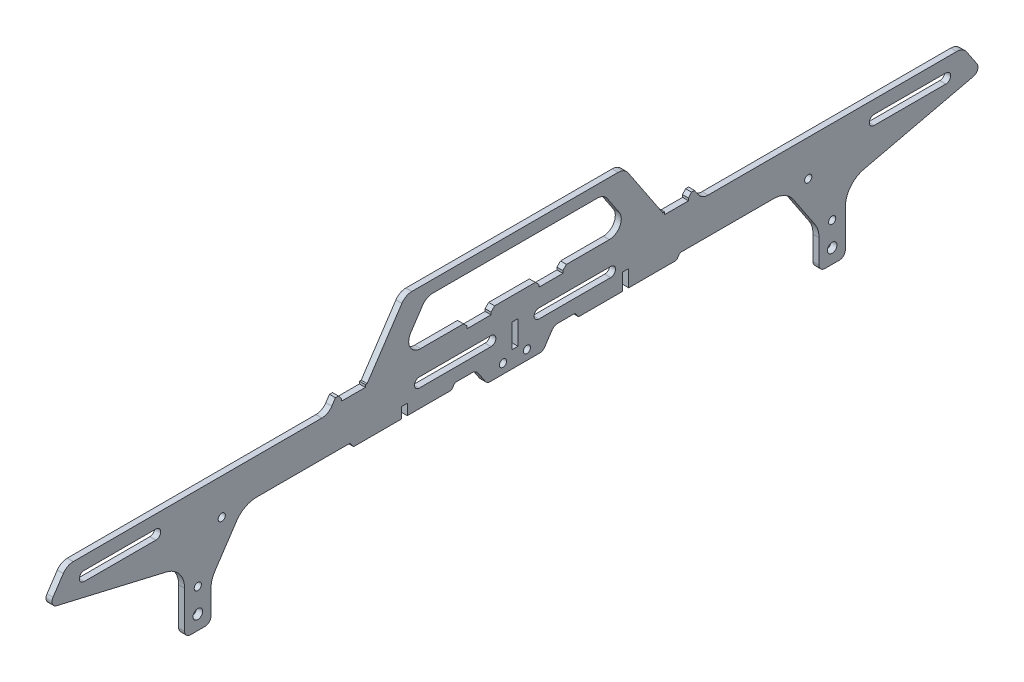
SolidWorks part; units mm, degrees
material "Stal węglowa"
ref_plane "Front" through (0, 0, 0) normal (0, 0, 1) x (1, 0, 0)
ref_plane "Top" through (0, 0, 0) normal (0, 1, 0) x (1, 0, 0)
ref_plane "Right" through (0, 0, 0) normal (1, 0, 0) x (0, 0, -1)
sketch "Szkic1" plane through (0, 0, 0) normal (1, 0, 0) x (0, 0, -1)
  line L78 (141.6289, -167.0231) -> (162.2864, -167.0231)
  line L79 (-197.7136, -134.0231) -> (-137.7136, -134.0231)
  line L80 (-197.7136, -142.0231) -> (-137.7136, -142.0231)
  line L81 (82.2864, -134.0231) -> (142.2864, -134.0231)
  line L82 (82.2864, -142.0231) -> (142.2864, -142.0231)
  line L83 (-206.7593, -123.0231) -> (0.9345, -123.0231)
  line L84 (-129.1697, -169.4172) -> (-220.6871, -148.0662)
  line L85 (438.2864, -220.0231) -> (438.2864, -188.8942)
  line L86 (412.9274, -188.9846) -> (394.8904, -161.9291)
  line L87 (378.2493, -153.0231) -> (301.0938, -153.0231)
  line L88 (242.2864, -134.0231) -> (182.2864, -134.0231)
  line L89 (531.332, -123.0231) -> (323.6382, -123.0231)
  line L90 (182.9438, -167.0231) -> (162.2864, -167.0231)
  line L91 (296.2864, -157.0231) -> (257.2864, -157.0231)
  line L92 (453.7424, -169.4172) -> (545.2598, -148.0662)
  line L93 (297.9505, -156.1325) -> (299.4297, -153.9137)
  line L94 (522.2864, -142.0231) -> (462.2864, -142.0231)
  line L95 (242.2864, -142.0231) -> (182.2864, -142.0231)
  line L96 (193.1718, -155.6949) -> (187.104, -164.7966)
  line L97 (522.2864, -134.0231) -> (462.2864, -134.0231)
  line L98 (72.2864, -148.0231) -> (72.2864, -157.0231)
  line L99 (67.2864, -157.0231) -> (67.2864, -148.0231)
  line L100 (67.2864, -148.0231) -> (72.2864, -148.0231)
  line L101 (252.2864, -157.0231) -> (252.2864, -143.0231)
  line L102 (252.2864, -157.0231) -> (216.2864, -157.0231)
  line L103 (252.2864, -143.0231) -> (257.2864, -143.0231)
  line L104 (257.2864, -143.0231) -> (257.2864, -157.0231)
  line L105 (162.2864, -114.0231) -> (179.2864, -114.0231)
  line L106 (159.7864, -153.0231) -> (164.7864, -153.0231)
  line L107 (159.7864, -133.0231) -> (164.7864, -133.0231)
  line L108 (164.7864, -133.0231) -> (164.7864, -153.0231)
  line L109 (159.7864, -153.0231) -> (159.7864, -133.0231)
  line L110 (239.4024, -83.4761) -> (249.4024, -98.4761)
  line L111 (162.2864, -79.0231) -> (231.0819, -79.0231)
  line L112 (162.2864, -69.0231) -> (248.4523, -69.0231)
  line L113 (256.7728, -73.4761) -> (285.8041, -117.0231)
  line L114 (162.2864, -79.0231) -> (93.4908, -79.0231)
  line L115 (85.1703, -83.4761) -> (75.1703, -98.4761)
  line L116 (162.2864, -69.0231) -> (76.1204, -69.0231)
  line L117 (312.2864, -114.0231) -> (315.3177, -118.5701)
  line L118 (287.2864, -119.0231) -> (307.2864, -119.0231)
  line L119 (205.2864, -114.0231) -> (241.0819, -114.0231)
  line L120 (182.2864, -117.0231) -> (182.2864, -119.0231)
  line L121 (182.2864, -119.0231) -> (202.2864, -119.0231)
  line L122 (202.2864, -119.0231) -> (202.2864, -117.0231)
  line L123 (548.2841, -140.4235) -> (539.6525, -127.4761)
  line L124 (-223.7113, -140.4235) -> (-215.0798, -127.4761)
  line L125 (214.6223, -156.1325) -> (213.1431, -153.9137)
  line L126 (211.479, -153.0231) -> (198.1641, -153.0231)
  line L127 (26.6223, -156.1325) -> (25.1431, -153.9137)
  line L128 (72.2864, -157.0231) -> (108.2864, -157.0231)
  line L129 (28.2864, -157.0231) -> (67.2864, -157.0231)
  line L130 (113.0938, -153.0231) -> (126.4086, -153.0231)
  line L131 (131.4009, -155.6949) -> (137.4687, -164.7966)
  line L132 (109.9505, -156.1325) -> (111.4297, -153.9137)
  line L133 (-53.6766, -153.0231) -> (23.479, -153.0231)
  line L134 (433.2864, -225.0231) -> (421.2864, -225.0231)
  line L135 (416.2864, -220.0231) -> (416.2864, -200.0786)
  line L136 (-91.7136, -220.0231) -> (-91.7136, -200.0786)
  line L137 (-113.7136, -220.0231) -> (-113.7136, -188.8942)
  line L138 (-108.7136, -225.0231) -> (-96.7136, -225.0231)
  line L139 (-88.3547, -188.9846) -> (-70.3176, -161.9291)
  line L140 (182.2864, -117.0231) -> (179.2864, -114.0231)
  line L141 (309.7864, -114.0231) -> (312.2864, -114.0231)
  line L142 (307.2864, -117.0231) -> (309.7864, -114.0231)
  line L143 (307.2864, -119.0231) -> (307.2864, -117.0231)
  line L144 (202.2864, -117.0231) -> (205.2864, -114.0231)
  line L145 (287.2864, -117.0231) -> (285.8041, -117.0231)
  line L146 (287.2864, -119.0231) -> (287.2864, -117.0231)
  line L147 (17.2864, -119.0231) -> (17.2864, -117.0231)
  line L148 (37.2864, -119.0231) -> (37.2864, -117.0231)
  line L149 (37.2864, -119.0231) -> (17.2864, -119.0231)
  line L150 (17.2864, -117.0231) -> (14.7864, -114.0231)
  line L151 (14.7864, -114.0231) -> (12.2864, -114.0231)
  line L152 (67.7999, -73.4761) -> (38.7686, -117.0231)
  line L153 (12.2864, -114.0231) -> (9.255, -118.5701)
  line L154 (37.2864, -117.0231) -> (38.7686, -117.0231)
  line L155 (142.2864, -117.0231) -> (142.2864, -119.0231)
  line L156 (122.2864, -119.0231) -> (122.2864, -117.0231)
  line L157 (119.2864, -114.0231) -> (83.4908, -114.0231)
  line L158 (142.2864, -117.0231) -> (145.2864, -114.0231)
  line L159 (122.2864, -117.0231) -> (119.2864, -114.0231)
  line L160 (162.2864, -114.0231) -> (145.2864, -114.0231)
  line L161 (142.2864, -119.0231) -> (122.2864, -119.0231)
  circle A22 centre (152.2864, -159.0231) radius 3
  circle A23 centre (-82.7136, -153.0231) radius 3
  arc A24 (-197.7136, -134.0231) -> (-197.7136, -142.0231) centre (-197.7136, -138.0231) ccw
  arc A25 (-137.7136, -142.0231) -> (-137.7136, -134.0231) centre (-137.7136, -138.0231) ccw
  arc A26 (82.2864, -134.0231) -> (82.2864, -142.0231) centre (82.2864, -138.0231) ccw
  arc A27 (142.2864, -142.0231) -> (142.2864, -134.0231) centre (142.2864, -138.0231) ccw
  arc A28 (-53.6766, -153.0231) -> (-70.3176, -161.9291) centre (-53.6766, -173.0231) ccw
  arc A29 (182.2864, -134.0231) -> (182.2864, -142.0231) centre (182.2864, -138.0231) ccw
  arc A30 (242.2864, -142.0231) -> (242.2864, -134.0231) centre (242.2864, -138.0231) ccw
  arc A31 (182.9438, -167.0231) -> (187.104, -164.7966) centre (182.9438, -162.0231) ccw
  circle A32 centre (407.2864, -153.0231) radius 3
  circle A33 centre (172.2864, -159.0231) radius 3
  arc A34 (296.2864, -157.0231) -> (297.9505, -156.1325) centre (296.2864, -155.0231) ccw
  arc A35 (462.2864, -134.0231) -> (462.2864, -142.0231) centre (462.2864, -138.0231) ccw
  arc A36 (301.0938, -153.0231) -> (299.4297, -153.9137) centre (301.0938, -155.0231) ccw
  arc A37 (453.7424, -169.4172) -> (438.2864, -188.8942) centre (458.2864, -188.8942) ccw
  circle A38 centre (427.2864, -193.0231) radius 3
  arc A39 (394.8904, -161.9291) -> (378.2493, -153.0231) centre (378.2493, -173.0231) ccw
  arc A40 (522.2864, -142.0231) -> (522.2864, -134.0231) centre (522.2864, -138.0231) ccw
  arc A41 (256.7728, -73.4761) -> (248.4523, -69.0231) centre (248.4523, -79.0231) ccw
  arc A42 (239.4024, -83.4761) -> (231.0819, -79.0231) centre (231.0819, -89.0231) ccw
  arc A43 (93.4908, -79.0231) -> (85.1703, -83.4761) centre (93.4908, -89.0231) ccw
  arc A44 (76.1204, -69.0231) -> (67.7999, -73.4761) centre (76.1204, -79.0231) ccw
  arc A45 (315.3177, -118.5701) -> (323.6382, -123.0231) centre (323.6382, -113.0231) ccw
  arc A46 (241.0819, -114.0231) -> (249.4024, -98.4761) centre (241.0819, -104.0231) ccw
  arc A47 (75.1703, -98.4761) -> (83.4908, -114.0231) centre (83.4908, -104.0231) ccw
  arc A48 (-206.7593, -123.0231) -> (-215.0798, -127.4761) centre (-206.7593, -133.0231) ccw
  arc A49 (545.2598, -148.0662) -> (548.2841, -140.4235) centre (544.1238, -143.197) ccw
  arc A50 (-223.7113, -140.4235) -> (-220.6871, -148.0662) centre (-219.5511, -143.197) ccw
  arc A51 (539.6525, -127.4761) -> (531.332, -123.0231) centre (531.332, -133.0231) ccw
  arc A52 (198.1641, -153.0231) -> (193.1718, -155.6949) centre (198.1641, -159.0231) ccw
  arc A53 (214.6223, -156.1325) -> (216.2864, -157.0231) centre (216.2864, -155.0231) ccw
  arc A54 (213.1431, -153.9137) -> (211.479, -153.0231) centre (211.479, -155.0231) ccw
  arc A55 (25.1431, -153.9137) -> (23.479, -153.0231) centre (23.479, -155.0231) ccw
  arc A56 (131.4009, -155.6949) -> (126.4086, -153.0231) centre (126.4086, -159.0231) ccw
  arc A57 (108.2864, -157.0231) -> (109.9505, -156.1325) centre (108.2864, -155.0231) ccw
  arc A58 (113.0938, -153.0231) -> (111.4297, -153.9137) centre (113.0938, -155.0231) ccw
  arc A59 (26.6223, -156.1325) -> (28.2864, -157.0231) centre (28.2864, -155.0231) ccw
  arc A60 (137.4687, -164.7966) -> (141.6289, -167.0231) centre (141.6289, -162.0231) ccw
  arc A61 (-113.7136, -188.8942) -> (-129.1697, -169.4172) centre (-133.7136, -188.8942) ccw
  circle A62 centre (427.2864, -213.0231) radius 4
  arc A63 (416.2864, -220.0231) -> (421.2864, -225.0231) centre (421.2864, -220.0231) ccw
  arc A64 (433.2864, -225.0231) -> (438.2864, -220.0231) centre (433.2864, -220.0231) ccw
  arc A65 (-113.7136, -220.0231) -> (-108.7136, -225.0231) centre (-108.7136, -220.0231) ccw
  circle A66 centre (-102.7136, -213.0231) radius 4
  circle A67 centre (-102.7136, -193.0231) radius 3
  arc A68 (416.2864, -200.0786) -> (412.9274, -188.9846) centre (396.2864, -200.0786) ccw
  arc A69 (-88.3547, -188.9846) -> (-91.7136, -200.0786) centre (-71.7136, -200.0786) ccw
  arc A70 (-96.7136, -225.0231) -> (-91.7136, -220.0231) centre (-96.7136, -220.0231) ccw
  arc A71 (0.9345, -123.0231) -> (9.255, -118.5701) centre (0.9345, -113.0231) ccw
extrude "Dodanie-wyciągnięcie1" add sketch "Szkic1" along normal blind 5
